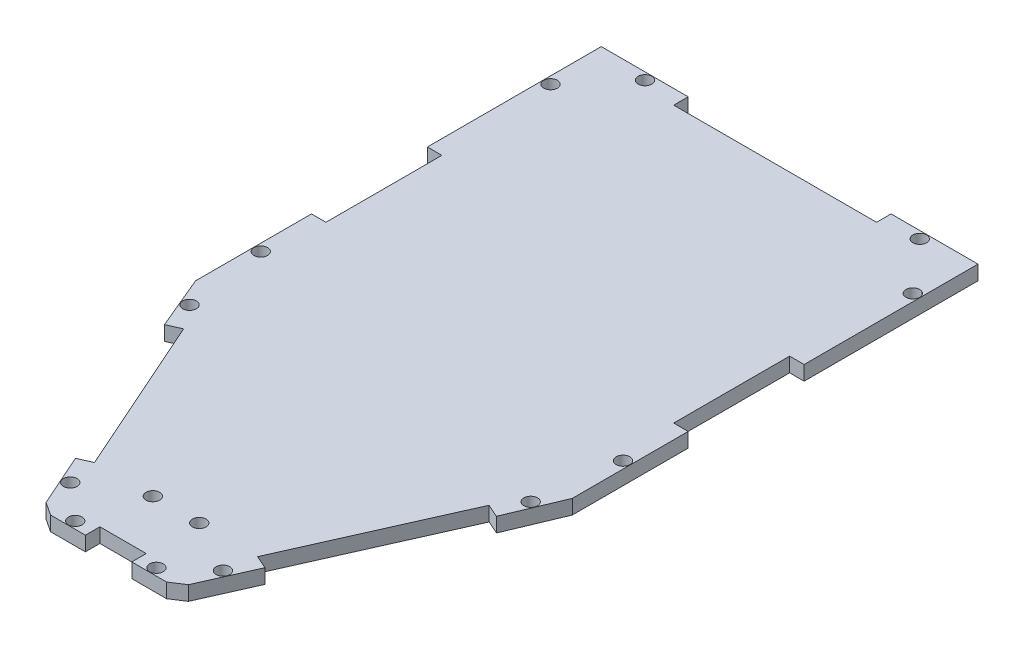
SolidWorks part; units mm, degrees
ref_plane "Front Plane" through (0, 0, 0) normal (0, 0, 1) x (1, 0, 0)
ref_plane "Top Plane" through (0, 0, 0) normal (0, 1, 0) x (1, 0, 0)
ref_plane "Right Plane" through (0, 0, 0) normal (1, 0, 0) x (0, 0, -1)
sketch "Sketch1" plane through (0, 0, 0) normal (0, 1, 0) x (1, 0, 0)
  line L0 (-41.275, 0) -> (-36.3683, -11.7139)
  line L1 (22.225, 85.725) -> (-22.225, 85.725)
  line L3 (-41.275, 88.9) -> (-22.225, 88.9)
  line L4 (22.225, 88.9) -> (22.225, 85.725)
  line L5 (41.275, 50.8) -> (41.275, 88.9)
  line L6 (-41.275, 0) -> (-38.1, 0) construction
  line L7 (-41.275, 50.8) -> (-38.1, 50.8)
  line L8 (0, 63.5) -> (0, -63.5) construction
  line L9 (38.1, 50.8) -> (38.1, 25.4)
  line L10 (-38.1, 50.8) -> (-38.1, 25.4)
  line L11 (-41.275, 50.8) -> (-41.275, 88.9)
  line L12 (41.275, 50.8) -> (38.1, 50.8)
  line L13 (-22.225, 88.9) -> (-22.225, 85.725)
  line L16 (41.275, 88.9) -> (22.225, 88.9)
  line L17 (-41.275, 0) -> (41.275, 0) construction
  line L18 (-38.1, 0) -> (-38.1, 25.4) construction
  line L19 (-38.1, 25.4) -> (-41.275, 25.4)
  line L21 (-41.275, 0) -> (-41.275, 25.4)
  line L22 (38.1, 25.4) -> (41.275, 25.4)
  line L23 (-38.1, 0) -> (-33.467, -10.4244) construction
  line L24 (41.275, 0) -> (41.275, 25.4)
  line L25 (33.467, -10.4244) -> (38.1, 0) construction
  line L26 (-36.3683, -11.7139) -> (-33.467, -10.4244) construction
  line L27 (41.275, 0) -> (36.3683, -11.7139)
  line L28 (36.3683, -11.7139) -> (33.467, -10.4244) construction
  line L29 (-17.858, -45.5446) -> (-12.7, -57.15) construction
  line L30 (-12.7, -57.15) -> (-15.6014, -58.4395) construction
  line L31 (-17.858, -45.5446) -> (-20.7593, -46.8341)
  line L32 (-15.6014, -58.4395) -> (-20.7593, -46.8341)
  line L33 (12.7, -57.15) -> (17.858, -45.5446) construction
  line L34 (-33.467, -10.4244) -> (-17.858, -45.5446)
  line L35 (-12.7, -57.15) -> (12.7, -57.15) construction
  line L36 (17.858, -45.5446) -> (33.467, -10.4244)
  line L38 (41.275, 69.85) -> (-41.275, 69.85) construction
  line L39 (12.7, -57.15) -> (15.6014, -58.4395) construction
  line L40 (17.858, -45.5446) -> (20.7593, -46.8341)
  line L41 (15.6014, -58.4395) -> (20.7593, -46.8341)
  line L42 (38.1, 0) -> (38.1, 25.4) construction
  line L43 (-15.6014, -58.4395) -> (-12.7, -60.325)
  line L44 (-5.08, -57.15) -> (-12.7, -57.15) construction
  line L45 (-5.08, -57.15) -> (-5.08, -60.325)
  line L46 (-5.08, -60.325) -> (-12.7, -60.325)
  line L47 (-12.7, -57.15) -> (-12.7, -60.325) construction
  line L48 (5.08, -57.15) -> (12.7, -57.15) construction
  line L49 (5.08, -57.15) -> (5.08, -60.325)
  line L50 (5.08, -60.325) -> (12.7, -60.325)
  line L51 (12.7, -57.15) -> (12.7, -60.325) construction
  line L52 (15.6014, -58.4395) -> (12.7, -60.325)
  line L53 (-5.08, -57.15) -> (5.08, -57.15)
  line L54 (33.467, -10.4244) -> (36.3683, -11.7139)
  line L55 (-33.467, -10.4244) -> (-36.3683, -11.7139)
  point P0 (0, 0)
  point P1 (0, -57.15)
  dimension "D1" = 25.4
  dimension "D2" = 57.15
  dimension "D3" = 3.175
  dimension "D4" = 82.55
  dimension "D5" = 3.175
  dimension "D6" = 19.05
  dimension "D8" = 38.1
  dimension "D9" = 50.8
  dimension "D10" = 25.4
  dimension "D11" = 12.7
  dimension "D12" = 12.7
  dimension "D13" = 10.16
extrude "Boss-Extrude1" add sketch "Sketch1" along normal blind 3.175
sketch "Sketch2" plane through (0, 0, 0) normal (0, -1, 0) x (-1, 0, 0)
  line L0 (39.6875, 50.8) -> (39.6875, 88.9) construction
  line L1 (41.275, 50.8) -> (38.1, 50.8) construction
  line L2 (22.225, 88.9) -> (41.275, 88.9) construction
  line L3 (0, 85.725) -> (0, -57.15) construction
  line L5 (41.275, 0) -> (36.3683, -11.7139) construction
  line L6 (-5.08, -58.7375) -> (-15.1428, -58.7375) construction
  line L7 (5.08, -57.15) -> (-5.08, -57.15) construction
  line L8 (-22.225, 85.725) -> (22.225, 85.725) construction
  line L10 (22.225, 88.9) -> (41.275, 88.9) construction
  line L11 (39.6875, 25.4) -> (39.6875, -3.7899) construction
  line L12 (38.1, 25.4) -> (41.275, 25.4) construction
  line L15 (41.275, 0) -> (36.3683, -11.7139) construction
  line L18 (34.9176, -11.0691) -> (41.275, 4.108) construction
  line L23 (36.3683, -11.7139) -> (33.467, -10.4244) construction
  line L24 (41.275, 25.4) -> (41.275, 0) construction
  line L25 (19.3086, -46.1893) -> (13.0261, -60.325) construction
  line L26 (17.858, -45.5446) -> (20.7593, -46.8341) construction
  line L27 (12.7, -60.325) -> (5.08, -60.325) construction
  line L28 (5.08, -58.7375) -> (15.1428, -58.7375) construction
  line L29 (5.08, -60.325) -> (5.08, -57.15) construction
  line L30 (15.6014, -58.4395) -> (12.7, -60.325) construction
  line L31 (-19.3086, -46.1893) -> (-13.0261, -60.325) construction
  line L32 (-34.9176, -11.0691) -> (-41.275, 4.108) construction
  line L33 (-39.6875, 25.4) -> (-39.6875, -3.7899) construction
  line L34 (-39.6875, 50.8) -> (-39.6875, 88.9) construction
  circle A0 centre (39.6875, 76.2) radius 1.5
  circle A1 centre (-8.89, -58.7375) radius 1.5
  circle A2 centre (39.6875, 12.7) radius 1.5
  circle A3 centre (37.3715, -5.2108) radius 1.5
  circle A4 centre (16.7297, -51.992) radius 1.5
  circle A5 centre (8.89, -58.7375) radius 1.5
  circle A6 centre (-16.7297, -51.992) radius 1.5
  circle A7 centre (-37.3715, -5.2108) radius 1.5
  circle A8 centre (-39.6875, 12.7) radius 1.5
  circle A9 centre (-39.6875, 76.2) radius 1.5
  dimension "D1" = 3
  dimension "D4" = 6.35
  dimension "D6" = 3.81
  dimension "D2" = 3
  dimension "D3" = 12.7
  dimension "D5" = 6.35
  dimension "D7" = 12.7
extrude "Cut-Extrude1" cut sketch "Sketch2" against normal through all
sketch "Sketch3" plane through (0, 0, 0) normal (0, -1, 0) x (1, 0, 0)
  line L0 (22.225, -87.3125) -> (41.275, -87.3125) construction
  line L1 (22.225, -88.9) -> (22.225, -85.725) construction
  line L2 (41.275, -50.8) -> (41.275, -88.9) construction
  line L3 (-22.225, -87.3125) -> (-41.275, -87.3125) construction
  line L4 (-22.225, -85.725) -> (-22.225, -88.9) construction
  line L5 (-41.275, -88.9) -> (-41.275, -50.8) construction
  circle A0 centre (-30.099, -87.3125) radius 1.5
  circle A1 centre (30.099, -87.3125) radius 1.5
  dimension "D1" = 3
  dimension "D2" = 7.874
  dimension "D3" = 7.874
extrude "Cut-Extrude2" cut sketch "Sketch3" against normal through all
sketch "Sketch4" plane through (0, 0, 0) normal (0, -1, 0) x (1, 0, 0)
  line L0 (17.858, 45.5446) -> (-17.858, 45.5446) construction
  line L1 (0, 57.15) -> (0, -85.725) construction
  line L2 (-5.08, 57.15) -> (5.08, 57.15) construction
  line L3 (22.225, -85.725) -> (-22.225, -85.725) construction
  circle A0 centre (5.08, 45.5446) radius 1.5
  circle A1 centre (-5.08, 45.5446) radius 1.5
  dimension "D1" = 3
  dimension "D2" = 3
  dimension "D3" = 5.08
  dimension "D4" = 5.08
extrude "Cut-Extrude3" cut sketch "Sketch4" against normal through all
